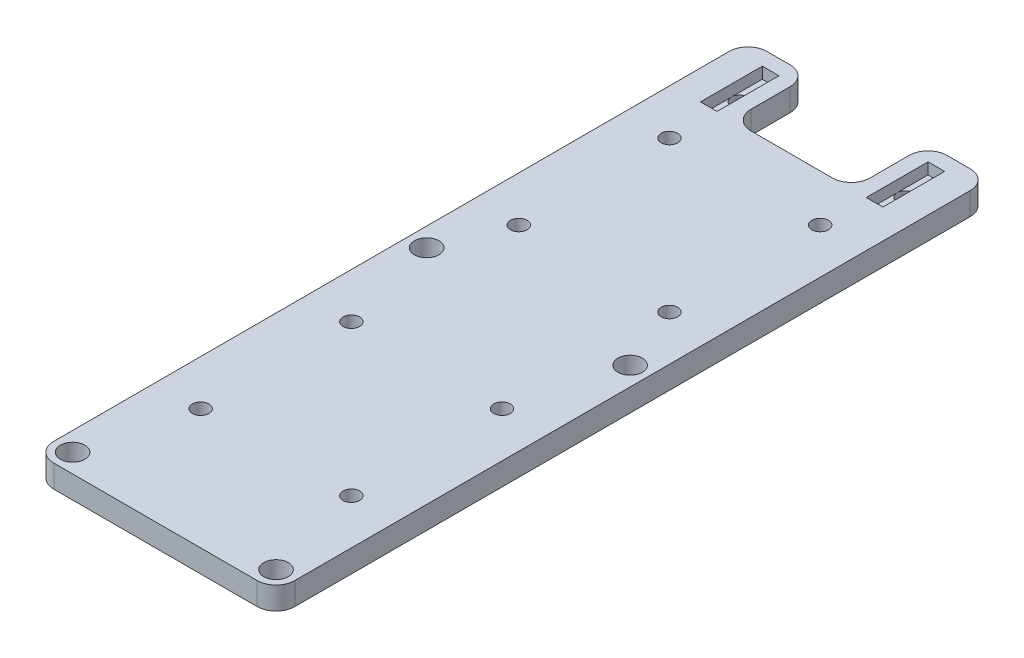
SolidWorks part; units mm, degrees
ref_plane "Front Plane" through (0, 0, 0) normal (0, 0, 1) x (1, 0, 0)
ref_plane "Top Plane" through (0, 0, 0) normal (0, 1, 0) x (1, 0, 0)
ref_plane "Right Plane" through (0, 0, 0) normal (1, 0, 0) x (0, 0, -1)
sketch "Sketch1" plane through (0, 0, 0) normal (0, 1, 0) x (1, 0, 0)
  line L0 (0, 42.225) -> (0, -42.225) construction
  line L1 (16, 42.225) -> (-16, 42.225)
  line L2 (16, 42.225) -> (16, -42.225)
  line L3 (16, -42.225) -> (-16, -42.225)
  line L4 (-16, 42.225) -> (-16, -42.225)
  line L5 (16, 42.225) -> (-16, -42.225) construction
  line L6 (16, -42.225) -> (-16, 42.225) construction
  line L12 (-12.1, 50.425) -> (-12.1, 52.425) construction
  line L17 (-11, 52.425) -> (-11, 42.225) construction
  line L18 (-7.9, 42.225) -> (-14.1, 42.225)
  line L20 (-10, 36) -> (10, 36)
  line L21 (-10, 36) -> (-10, 16)
  line L22 (-10, 16) -> (10, 16)
  line L23 (10, 36) -> (10, 16)
  line L24 (-10, 36) -> (10, 16) construction
  line L25 (-10, 16) -> (10, 36) construction
  line L26 (-14.5, 10.775) -> (14.5, 10.775)
  line L27 (-14.5, 10.775) -> (-14.5, 41.225)
  line L28 (-14.5, 41.225) -> (14.5, 41.225)
  line L29 (14.5, 10.775) -> (14.5, 41.225)
  line L30 (-14.5, 10.775) -> (14.5, 41.225) construction
  line L31 (-14.5, 41.225) -> (14.5, 10.775) construction
  line L32 (-10, -6.225) -> (10, -6.225)
  line L33 (-10, -6.225) -> (-10, -26.225)
  line L34 (-10, -26.225) -> (10, -26.225)
  line L35 (10, -6.225) -> (10, -26.225)
  line L36 (-10, -6.225) -> (10, -26.225) construction
  line L37 (-10, -26.225) -> (10, -6.225) construction
  line L38 (-15.75, -36.225) -> (15.75, -36.225)
  line L39 (-15.75, -36.225) -> (-15.75, 3.775)
  line L40 (-15.75, 3.775) -> (15.75, 3.775)
  line L41 (15.75, -36.225) -> (15.75, 3.775)
  line L42 (-15.75, -36.225) -> (15.75, 3.775) construction
  line L43 (-15.75, 3.775) -> (15.75, -36.225) construction
  line L48 (-7.9, 42.225) -> (-7.9, 52.425)
  line L49 (-7.9, 52.425) -> (-14.1, 52.425)
  line L59 (-14.1, 42.225) -> (-14.1, 52.425)
  line L63 (-12.1, 50.425) -> (-9.9, 50.425)
  line L64 (-12.1, 50.425) -> (-12.1, 42.225)
  line L65 (-12.1, 42.225) -> (-9.9, 42.225)
  line L66 (-9.9, 50.425) -> (-9.9, 42.225)
  line L67 (-12.1, 50.425) -> (-9.9, 42.225) construction
  line L68 (-12.1, 42.225) -> (-9.9, 50.425) construction
  line L69 (-12.1, 50.425) -> (-14.1, 50.425) construction
  line L74 (7.9, 42.225) -> (14.1, 42.225)
  line L75 (14.1, 42.225) -> (14.1, 52.425)
  line L76 (7.9, 52.425) -> (14.1, 52.425)
  line L77 (7.9, 42.225) -> (7.9, 52.425)
  line L78 (12.1, 50.425) -> (9.9, 50.425)
  line L79 (12.1, 50.425) -> (12.1, 42.225)
  line L80 (12.1, 42.225) -> (9.9, 42.225)
  line L81 (9.9, 50.425) -> (9.9, 42.225)
  line L82 (-14.5, 10.775) -> (-14.5, 3.775) construction
  line L83 (-14.5, 7.275) -> (16, 7.275) construction
  line L89 (-13.5, -37.225) -> (-16, -37.225) construction
  line L94 (-14.1, 52.425) -> (-16, 52.425)
  line L95 (-14.1, 52.425) -> (-14.1, 42.225)
  line L96 (-14.1, 42.225) -> (-16, 42.225)
  line L97 (-16, 52.425) -> (-16, 42.225)
  line L98 (14.1, 52.425) -> (16, 52.425)
  line L99 (14.1, 52.425) -> (14.1, 42.225)
  line L100 (14.1, 42.225) -> (16, 42.225)
  line L101 (16, 52.425) -> (16, 42.225)
  circle A3 centre (-10, 36) radius 1.1
  circle A4 centre (10, 36) radius 1.1
  circle A5 centre (10, 16) radius 1.1
  circle A6 centre (-10, 16) radius 1.1
  circle A7 centre (-10, -6.225) radius 1.1
  circle A8 centre (10, -6.225) radius 1.1
  circle A9 centre (10, -26.225) radius 1.1
  circle A10 centre (-10, -26.225) radius 1.1
  circle A37 centre (-13.5, 7.275) radius 2.5
  circle A38 centre (-13.5, 7.275) radius 1.625
  circle A39 centre (13.5, 7.275) radius 1.625
  circle A40 centre (-13.5, -39.725) radius 2.5
  circle A41 centre (-13.5, -39.725) radius 1.625
  circle A42 centre (13.5, -39.725) radius 1.625
  point P0 (0, 0)
  point P8 (0, 0)
  point P16 (0, 26)
  point P26 (0, 26)
  point P31 (0, -16.225)
  point P36 (0, -16.225)
  point P61 (-11, 46.325)
  dimension "D3" = 2
  dimension "D17" = 2.2
  dimension "D22" = 5
  dimension "D23" = 3.25
  dimension "D8" = 32
  dimension "D9" = 22
  dimension "D10" = 20
  dimension "D11" = 29
  dimension "D12" = 30.45
  dimension "D13" = 40
  dimension "D14" = 31.5
  dimension "D15" = 1
  dimension "D16" = 7
  dimension "D18" = 2.2
  dimension "D20" = 8.2
  dimension "D24" = 1
extrude "Boss-Extrude1" add sketch "Sketch1" along normal blind 3 contours L63 L66 L1 L48 L49 L59 L18 L64 | L81 L78 L79 L1 L75 L76 L77 | L94 L97 L1 L59 | L101 L98 L75 L1 | L1 L4 L3 L2 | A4 | A3 | A7 | A8 | A9 | A10 | A5 | A6 | A39 | A38 | A41 | A42 region at (15.05, 0, -47.325) region at (13.1, 0, -42.3444) region at (-8.9, 0, -42.3444) region at (-15.05, 0, -47.325)
sketch "Sketch2" plane through (0, 0, 0) normal (0, -1, 0) x (1, 0, 0)
  line L0 (-12.1, -42.225) -> (-9.9, -50.425) construction
  line L1 (12.1, -42.225) -> (9.9, -50.425) construction
  line L4 (12.1, -42.225) -> (9.9, -42.225)
  line L5 (12.1, -50.425) -> (12.1, -42.225)
  line L6 (9.9, -50.425) -> (12.1, -50.425)
  line L7 (9.9, -42.225) -> (9.9, -50.425)
  line L8 (12.1, -42.225) -> (9.9, -42.225)
  line L9 (12.1, -50.425) -> (12.1, -42.225)
  line L10 (9.9, -50.425) -> (12.1, -50.425)
  line L11 (9.9, -42.225) -> (9.9, -50.425)
  line L12 (-9.9, -42.225) -> (-12.1, -42.225)
  line L13 (-9.9, -50.425) -> (-9.9, -42.225)
  line L14 (-12.1, -50.425) -> (-9.9, -50.425)
  line L15 (-12.1, -42.225) -> (-12.1, -50.425)
  line L16 (-9.9, -42.225) -> (-12.1, -42.225)
  line L17 (-9.9, -50.425) -> (-9.9, -42.225)
  line L18 (-12.1, -50.425) -> (-9.9, -50.425)
  line L19 (-12.1, -42.225) -> (-12.1, -50.425)
  circle A0 centre (-11, -46.325) radius 1.1
  circle A1 centre (11, -46.325) radius 1.1
  line M9 (9.9, -42.225) -> (12.1, -42.225)
  line M10 (12.1, -42.225) -> (12.1, -50.425)
  line M11 (12.1, -50.425) -> (9.9, -50.425)
  line M12 (9.9, -50.425) -> (9.9, -42.225)
  line M13 (-12.1, -42.225) -> (-9.9, -42.225)
  line M14 (-9.9, -42.225) -> (-9.9, -50.425)
  line M15 (-9.9, -50.425) -> (-12.1, -50.425)
  line M16 (-12.1, -50.425) -> (-12.1, -42.225)
  dimension "D1" = 0
  dimension "D2" = 0
extrude "Boss-Extrude2" add sketch "Sketch2" against normal offset from surface (1.5 mm away) 1.5 contours A0 L19 M14 M13 | A0 L17 M16 M15 | A1 L9 M12 M11 | A1 L11 M10 M9 region at (11, 0, -43.8523) region at (11, 0, -48.7977) region at (-11, 0, -43.8523) region at (-11, 0, -48.7977) up to face at (11, 3, -46.325)
fillet "Fillet1" radius 2.5 8 edges at (7.9, 1.5, -42.225) (-7.9, 1.5, -42.225) (-16, 1.5, -52.425) (-7.9, 1.5, -52.425) (7.9, 1.5, -52.425) (16, 1.5, -52.425) (-16, 1.5, 42.225) (16, 1.5, 42.225)
